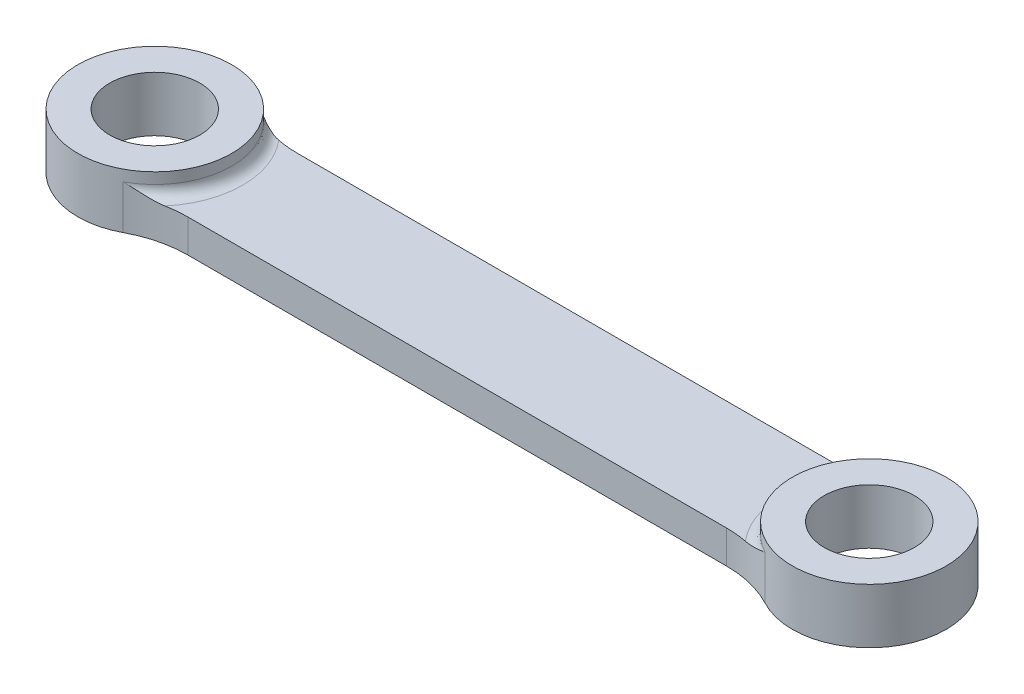
SolidWorks part; units mm, degrees
ref_plane "前视基准面" through (0, 0, 0) normal (0, 0, 1) x (1, 0, 0)
ref_plane "上视基准面" through (0, 0, 0) normal (0, 1, 0) x (1, 0, 0)
ref_plane "右视基准面" through (0, 0, 0) normal (1, 0, 0) x (0, 0, -1)
sketch "Sketch2" plane through (0, 0, 0) normal (0, 1, 0) x (1, 0, 0)
  line L0 (0, 0) -> (65, 0) construction
  line L1 (0, 5) -> (65, 5)
  line L2 (0, -5) -> (65, -5)
  arc A0 (0, 5) -> (0, -5) centre (0, 0) ccw
  arc A1 (65, -5) -> (65, 5) centre (65, 0) ccw
  point P3 (32.5, 0)
  dimension "D2" = 5
  dimension "D1" = 65
extrude "Boss-Extrude1" add sketch "Sketch2" along normal blind 3
sketch "Sketch3" plane through (0, 0, 0) normal (0, -1, 0) x (1, 0, 0)
  circle A0 centre (0, 0) radius 7
  circle A1 centre (65, 0) radius 7
  dimension "D1" = 14
  dimension "D2" = 14
extrude "Boss-Extrude2" add sketch "Sketch3" against normal blind 5
sketch "Sketch4" plane through (0, 5, 0) normal (0, 1, 0) x (1, 0, 0)
  circle A0 centre (0, 0) radius 4.1
  circle A1 centre (65, 0) radius 4.1
  dimension "D1" = 8.2
  dimension "D2" = 8.2
extrude "Cut-Extrude1" cut sketch "Sketch4" against normal through all
fillet "Fillet1" radius 10 4 edges at (4.899, 1.5, -5) (60.101, 1.5, -5) (60.101, 1.5, 5) (4.899, 1.5, 5)
fillet "Fillet2" radius 1 2 edges at (7, 3, 0) (58, 3, 0)
